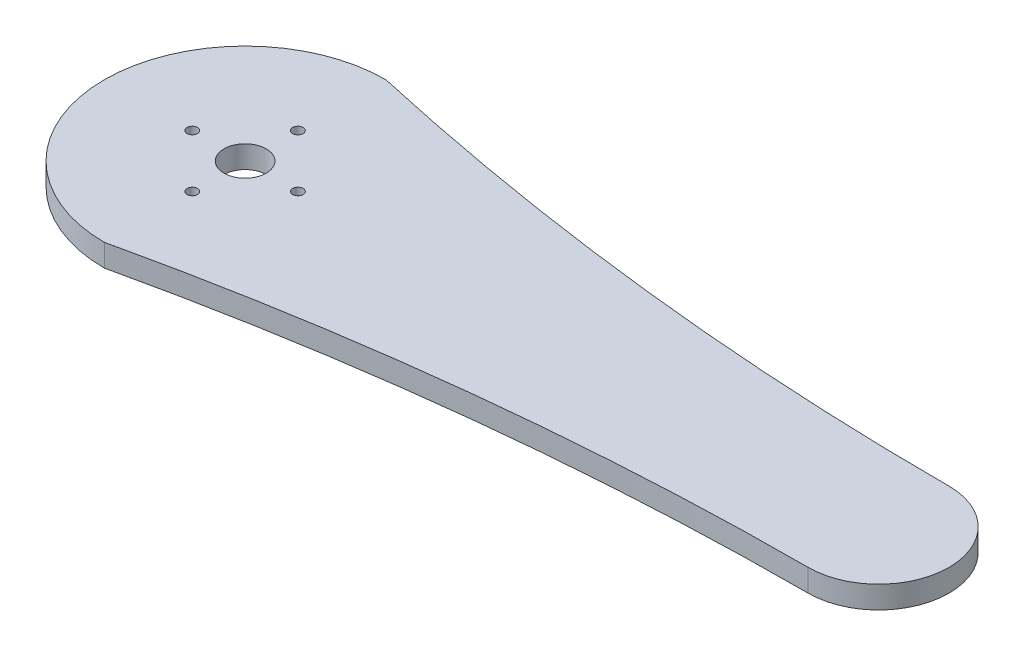
SolidWorks part; units mm, degrees
material "Pine"
ref_plane "Front Plane" through (0, 0, 0) normal (0, 0, 1) x (1, 0, 0)
ref_plane "Top Plane" through (0, 0, 0) normal (0, 1, 0) x (1, 0, 0)
ref_plane "Right Plane" through (0, 0, 0) normal (1, 0, 0) x (0, 0, -1)
sketch "Sketch3" plane through (0, 0, 0) normal (0, 1, 0) x (1, 0, 0)
  line L0 (-40.3723, 0) -> (-32.1223, 0) construction
  arc A0 (-40.3723, 20) -> (-40.3723, -20) centre (-40.3723, 0) ccw
  circle A2 centre (-40.3723, 0) radius 3
  circle A3 centre (-32.8723, 0) radius 0.75
  circle A8 centre (-47.8723, 0) radius 0.75
  circle A9 centre (-40.3723, 7.5) radius 0.75
  circle A10 centre (-40.3723, -7.5) radius 0.75
  arc A11 (49.6277, 10) -> (49.6277, -10) centre (49.6277, 0) cw
  arc A12 (49.6277, 10) -> (-40.3723, 20) centre (49.6277, 420) cw
  arc A13 (49.6277, -10) -> (-40.3723, -20) centre (49.6277, -420) ccw
  point P3 (-0.3723, 0)
  dimension "D1" = 20
  dimension "D7" = 6
  dimension "D9" = 1.5
  dimension "D11" = 1.5
  dimension "D14" = 1.5
  dimension "D15" = 1.5
  dimension "D3" = 10
  dimension "D2" = 90
  dimension "D10" = 7.5
  dimension "D12" = 7.5
  dimension "D13" = 7.5
  dimension "D16" = 7.5
extrude "Boss-Extrude1" add sketch "Sketch3" along normal blind 3.175
